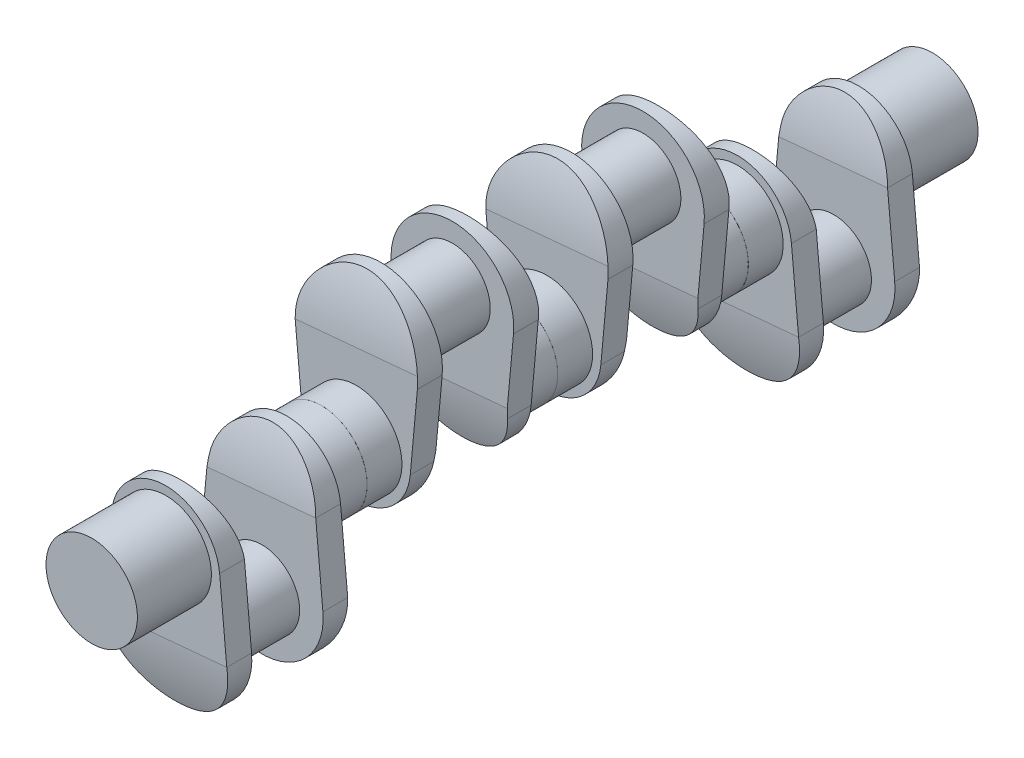
SolidWorks part; units mm, degrees
ref_plane "Front Plane" through (0, 0, 0) normal (0, 0, 1) x (1, 0, 0)
ref_plane "Top Plane" through (0, 0, 0) normal (0, 1, 0) x (1, 0, 0)
ref_plane "Right Plane" through (0, 0, 0) normal (1, 0, 0) x (0, 0, -1)
sketch "Sketch1" plane through (0, 0, 0) normal (0, 0, 1) x (1, 0, 0)
  line L0 (0, 0) -> (75071.7954, 0) construction
  line L1 (0, 0) -> (0, -75071.7954) construction
  line L2 (-41.3253, 3.8042) -> (-46.8021, -55.6917)
  line L3 (41.3253, 3.8042) -> (46.8021, -55.6917)
  circle A0 centre (0, 0) radius 35
  arc A1 (41.5, 0) -> (-41.5, 0) centre (0, 0) ccw
  circle A2 centre (0, -60) radius 47
  dimension "D1" = 70
  dimension "D2" = 83
  dimension "D3" = 94
  dimension "D4" = 60
extrude "Boss-Extrude1" add sketch "Sketch1" along normal blind 26.67 contours A2 A0 | A0 A2 region at (0, -23.6567, 0) region at (0, 6.5195, 0)
extrude "Boss-Extrude2" add sketch "Sketch1<3>" against normal blind 19 contours A2 L3 A1 L2 A0 | A2 A0 | A2 A0 | A0 A2 region at (0, 40.1506, 0) region at (0, -64.9469, 0) region at (0, -23.6567, 0) region at (0, 6.5195, 0)
sketch "Sketch1<3>" plane through (0, 0, 0) normal (0, 0, 1) x (1, 0, 0) same geometry as "Sketch1"
sketch "Sketch3" plane through (0, 0, -19) normal (0, 0, -1) x (-1, 0, 0)
  circle A0 centre (0, -63.5) radius 29
  dimension "D1" = 58
  dimension "D2" = 63.5
extrude "Boss-Extrude3" add sketch "Sketch3" along normal blind 27.31
sketch "Sketch4" plane through (41.3253, 3.8042, 0) normal (0.9958, 0.0917, 0) x (0, 0, -1)
  line L0 (0, -106.7474) -> (19, -106.7474) construction
  line L1 (19, 41.5) -> (0, 41.5) construction
  line L2 (9.5, 41.5) -> (32.8589, 41.5)
  line L3 (32.8589, 41.5) -> (32.8589, 0)
  line L4 (19, 0) -> (32.8589, 0)
  line L5 (19, 0) -> (0, 0) construction
  line L6 (19, 0) -> (19, 41.5) construction
  line L7 (0, -59.7474) -> (-12.4859, -59.7474)
  line L8 (-12.4859, -59.7474) -> (-12.4859, -106.7474)
  line L9 (-12.4859, -106.7474) -> (9.5, -106.7474)
  arc A0 (0, -59.7474) -> (9.5, -106.7474) centre (168.7246, -50.1036) ccw
  arc A1 (19, 0) -> (9.5, 41.5) centre (-149.1767, -16.6609) ccw
  dimension "D1" = 169
  dimension "D2" = 169
extrude "Cut-Extrude1" cut sketch "Sketch4" against normal through all
mirror "Mirror3" about plane through (0, -63.5, -46.31) normal (0, 0, -1) of bodies 104
pattern_linear "LPattern1" count 3 spacing 146 along (0, 0, -1) of bodies 107
ref_axis "Axis1" through (0, 0, 299.3535) along (0, 0, -1)
move or copy body "Body-Move/Copy1" bodies to move or copy 109 copy no rotation origin (0, 0, 0) rotation axis (0, 0, -1) rotation angle 120
move or copy body "Body-Move/Copy2" bodies to move or copy 110 copy no rotation origin (0, 0, 0) rotation axis (0, 0, 1) rotation angle 120
sketch "Sketch5" plane through (0, 0, 26.67) normal (0, 0, 1) x (1, 0, 0)
  circle A1 centre (0, 0) radius 35
  circle A2 centre (0, 0) radius 35
  dimension "D1" = 0
extrude "Boss-Extrude4" add sketch "Sketch5" along normal blind 30
move or copy body "Body-Move/Copy7" bodies to move or copy 111 copy no rotation origin (0, 0, 0) rotation axis (0, 0, -1) rotation angle 60
move or copy body "Body-Move/Copy8" bodies to move or copy 112 copy no rotation origin (0, 0, 0) rotation axis (0, 0, 1) rotation angle 60
move or copy body "Body-Move/Copy9" bodies to move or copy 122 copy yes number of copies 1 translate (0, 0, -146) parameters "D1"=0, "D2"=0, "D3"=146
move or copy body "Body-Move/Copy10" bodies to move or copy 123 copy no rotation origin (0, 0, 0) rotation axis (0, 0, 1) rotation angle 180
sketch "Sketch8" plane through (0, 0, -557.29) normal (0, 0, -1) x (-1, 0, 0)
  circle A0 centre (0, 0) radius 35
extrude "Boss-Extrude6" add sketch "Sketch8" along normal blind 30
sketch "Sketch9" plane through (0, 0, -587.29) normal (0, 0, -1) x (-1, 0, 0)
  line L0 (-121.1656, 0) -> (121.1656, 0) construction
  point P5 (0, 0)
